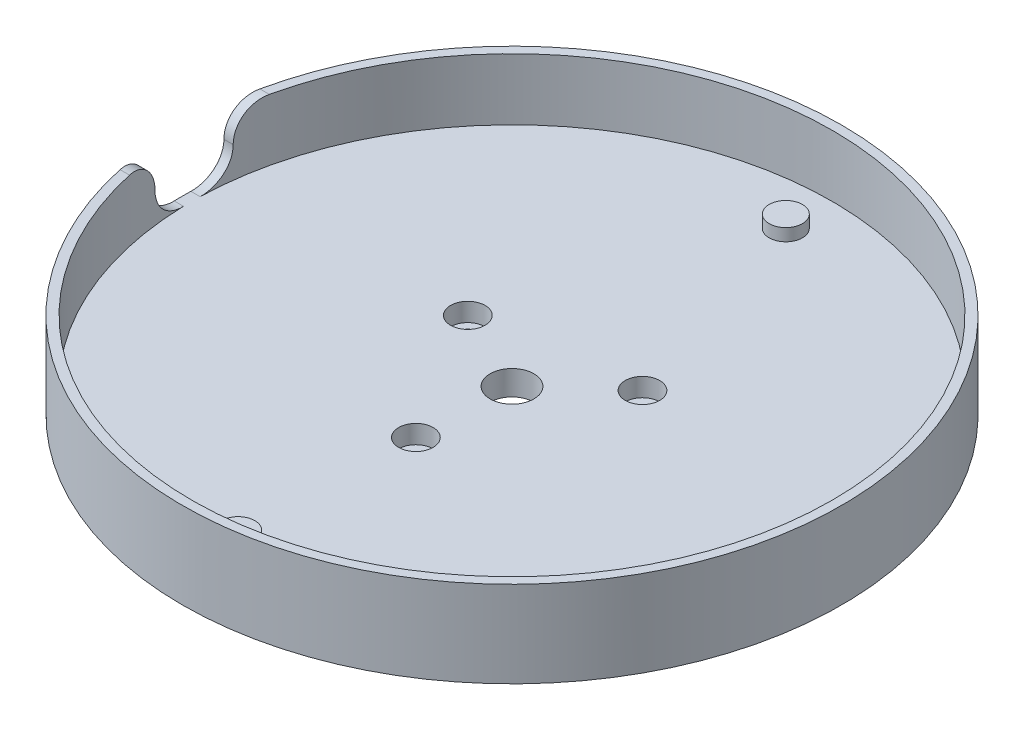
SolidWorks part; units mm, degrees
ref_plane "Front Plane" through (0, 0, 0) normal (0, 0, 1) x (1, 0, 0)
ref_plane "Top Plane" through (0, 0, 0) normal (0, 1, 0) x (1, 0, 0)
ref_plane "Right Plane" through (0, 0, 0) normal (1, 0, 0) x (0, 0, -1)
sketch "Sketch1" plane through (0, 0, 0) normal (0, 1, 0) x (1, 0, 0)
  circle A0 centre (0, 0) radius 53.5
  dimension "D1" = 107
extrude "Boss-Extrude1" add sketch "Sketch1" along normal blind 2
sketch "Sketch2" plane through (0, 2, 0) normal (0, 1, 0) x (1, 0, 0)
  circle A0 centre (0, -44.45) radius 2.7
  circle A1 centre (0, 44.45) radius 2.7
  dimension "D1" = 5.4
  dimension "D2" = 5.4
  dimension "D3" = 88.9
  dimension "D4" = 44.45
extrude "Boss-Extrude2" add sketch "Sketch2" along normal blind 2
sketch "Sketch3" plane through (0, 2, 0) normal (0, 1, 0) x (1, 0, 0)
  circle A0 centre (0, 0) radius 3.55
  dimension "D1" = 7.1
extrude "Cut-Extrude1" cut sketch "Sketch3" against normal blind 2 contours A0
sketch "Sketch7" plane through (0, 2, 0) normal (0, 1, 0) x (1, 0, 0)
  circle A0 centre (0, 0) radius 53.5
  circle A1 centre (0, 0) radius 52
  dimension "D1" = 107
  dimension "D2" = 104
extrude "Boss-Extrude3" add sketch "Sketch7" along normal blind 10
sketch "Sketch8" plane through (0, 2, 0) normal (0, 1, 0) x (1, 0, 0)
  line L0 (0, -6.35) -> (0, 6.35)
  line L1 (0, 6.35) -> (-56.6518, 6.35)
  line L3 (0, -6.35) -> (-56.6518, -6.35)
  line L4 (-56.6518, 6.35) -> (-56.6518, -6.35)
  line L5 (0, -6.35) -> (0, 6.35) construction
  line L6 (0, 0) -> (-56.6518, 0) construction
  point P0 (0, 0)
  dimension "D1" = 12.7
extrude "Cut-Extrude4" cut sketch "Sketch8" along normal up to surface (10 mm away) contours L4 L3 L0 L1 up to face at (0, 12, 53.5)
sketch "Sketch12" plane through (0, 2, 0) normal (0, 1, 0) x (1, 0, 0)
  circle A0 centre (11.169, 10.0127) radius 2.8
  circle A1 centre (-0.6161, -14.9873) radius 2.8
  circle A2 centre (-13.568, 6.396) radius 2.8
  circle A3 centre (0, 0) radius 3.55 construction
  dimension "D3" = 15
  dimension "D4" = 5.6
  dimension "D5" = 5.6
  dimension "D6" = 5.6
  dimension "D7" = 25
  dimension "D8" = 25
  dimension "D9" = 25
  dimension "D1" = 15
  dimension "D2" = 15
sketch "Sketch13" plane through (0, 0, 0) normal (0, -1, 0) x (1, 0, 0)
  circle A0 centre (0, 0) radius 53.5
  circle A1 centre (0, 0) radius 3.55
extrude "Boss-Extrude4" add sketch "Sketch13" along normal blind 2
extrude "Cut-Extrude6" cut sketch "Sketch12" against normal blind 3 contours A2 | A1 | A0
sketch "Sketch16" plane through (0, -1, 0) normal (0, 1, 0) x (1, 0, 0)
  circle A0 centre (11.169, 10.0127) radius 1.5
  circle A1 centre (-0.6161, -14.9873) radius 1.5
  circle A2 centre (-13.568, 6.396) radius 1.5
  dimension "D1" = 3
  dimension "D2" = 3
  dimension "D3" = 3
extrude "Cut-Extrude8" cut sketch "Sketch16" against normal through all contours A2 | A1 | A0
fillet "Fillet3" radius 5 4 edges at (-52.3663, 12, -6.35) (-52.3663, 12, 6.35) (-52.3663, 2, 6.35) (-52.3663, 2, -6.35)
